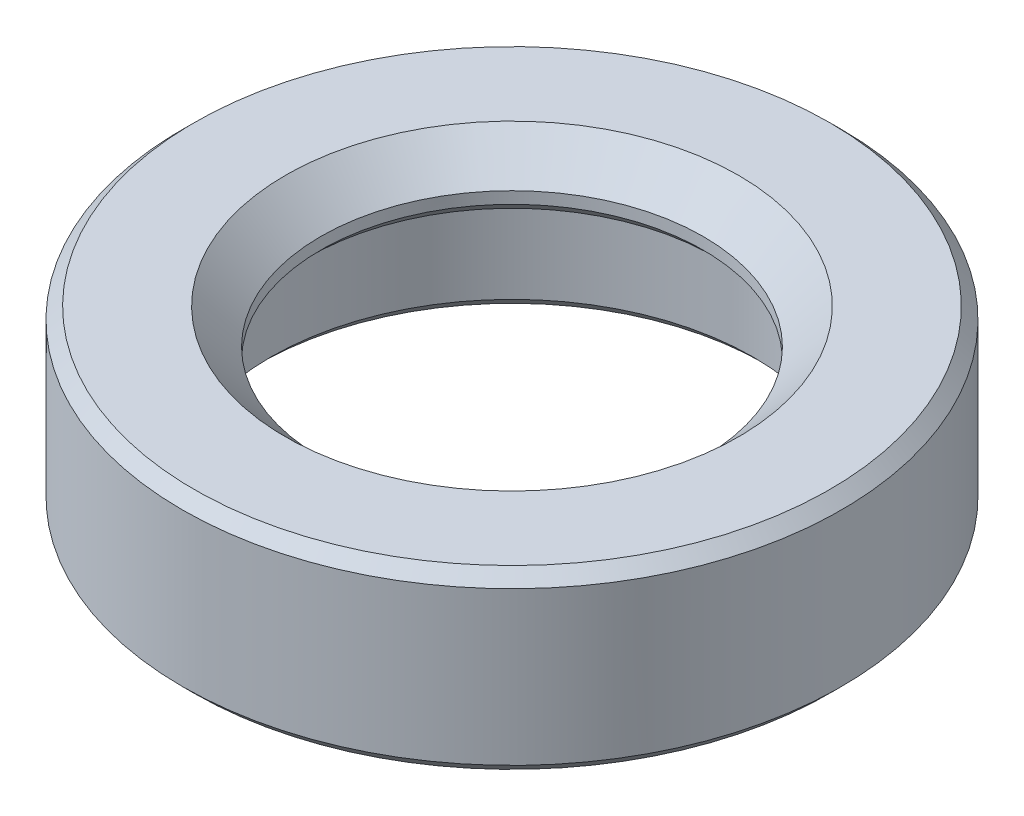
SolidWorks part; units mm, degrees
ref_plane "Ebene vorne" through (0, 0, 0) normal (0, 0, 1) x (1, 0, 0)
ref_plane "Ebene oben" through (0, 0, 0) normal (0, 1, 0) x (1, 0, 0)
ref_plane "Ebene rechts" through (0, 0, 0) normal (1, 0, 0) x (0, 0, -1)
sketch "Skizze1" plane through (0, 0, 0) normal (1, 0, 0) x (0, 0, -1)
  line L0 (0, 14.193) -> (0, -13.0854) construction
  line L1 (-15.1899, 0) -> (14.6519, 0) construction
  line L2 (4.1, -1.5) -> (4.1, 0.5)
  line L3 (4.1, 0.5) -> (3.25, 0.5)
  line L4 (3.25, 0.5) -> (3.25, 1.5)
  line L5 (3.25, 1.5) -> (5.6, 1.5)
  line L6 (5.6, 1.5) -> (5.6, -1.5)
  line L7 (5.6, -1.5) -> (4.1, -1.5)
  dimension "D1" = 11.2
  dimension "D2" = 8.2
  dimension "D3" = 2
  dimension "D4" = 3
  dimension "D5" = 6.5
revolve "Rotation1" add sketch "Skizze1" angle 360 about L0
ref_axis "Achse1" through (0, -14.4494, 0) along (0, 1, 0)
chamfer "Fase1" distance 0.2 angle 45 4 edges at (0, 0.5, 3.25) (0, -1.5, 4.1) (0, -1.5, 5.6) (0, 1.5, 5.6)
chamfer "Fase2" distance 0.6 angle 45 1 edges at (0, 1.5, 3.25)
